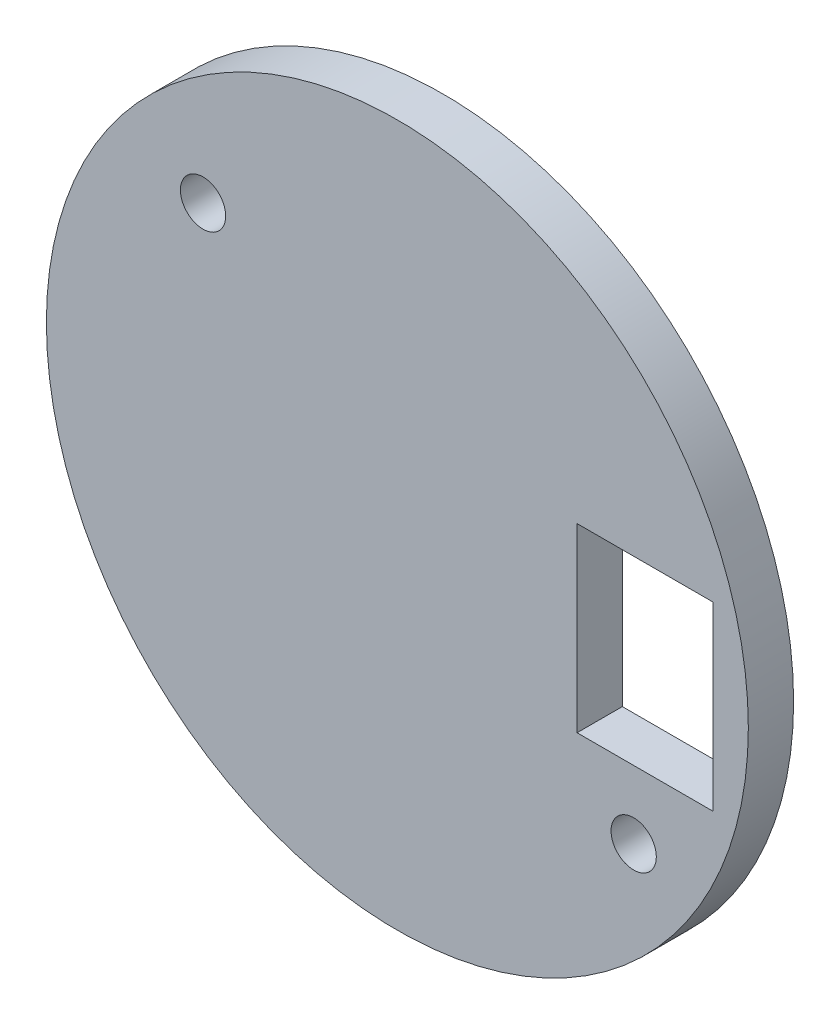
SolidWorks part; units mm, degrees
ref_plane "Top Plane" through (0, 0, 0) normal (0, 0, 1) x (1, 0, 0)
ref_plane "Right Plane" through (0, 0, 0) normal (0, 1, 0) x (1, 0, 0)
ref_plane "Front Plane" through (0, 0, 0) normal (1, 0, 0) x (0, 0, -1)
ref_axis "x-axis" through (-88.99, 0, 0) along (1, 0, 0)
ref_axis "y-axis" through (0, -55, 0) along (0, 1, 0)
ref_axis "z-axis" through (0, 0, 55) along (0, 0, -1)
sketch "Sketch1" plane through (0, 0, 0) normal (0, 0, 1) x (0, -1, 0)
  line L5 (-4, 7.9307) -> (0, 7.9307) construction
  line L6 (0, 7.0768) -> (4, 7.0768) construction
  line L7 (0, -14) -> (0, -15.5) construction
  line L8 (-0.0257, 13.9362) -> (-0.0257, 15.4362) construction
  line L9 (-4.0257, 13.9362) -> (3.9743, 13.9362)
  line L10 (-4.0257, 13.9362) -> (-4.0257, 7.9362)
  line L11 (-4.0257, 7.9362) -> (3.9743, 7.9362)
  line L12 (3.9743, 13.9362) -> (3.9743, 7.9362)
  line L13 (-4.0257, 9.9362) -> (-7.0257, 9.9362) construction
  line L14 (6.9743, 10.436) -> (3.9743, 10.436) construction
  circle A0 centre (0, 0) radius 15.5
  circle A3 centre (6.9743, 10.436) radius 1
  circle A5 centre (-8.0257, -8.5809) radius 1
  dimension "D1" = 31
  dimension "D5" = 2
  dimension "D6" = 2
  dimension "D2" = 2
  dimension "D3" = 2.4998
  dimension "D4" = 1.5
extrude "Boss-Extrude1" add sketch "Sketch1" along normal blind 2
